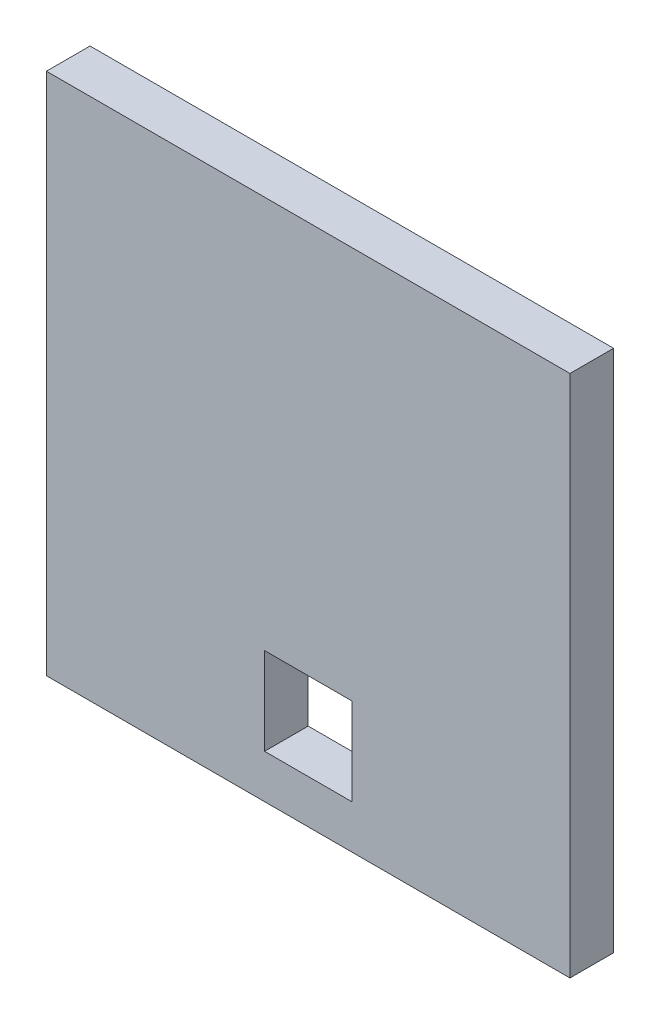
SolidWorks part; units mm, degrees
ref_plane "Front Plane" through (0, 0, 0) normal (0, 0, 1) x (1, 0, 0)
ref_plane "Top Plane" through (0, 0, 0) normal (0, 1, 0) x (1, 0, 0)
ref_plane "Right Plane" through (0, 0, 0) normal (1, 0, 0) x (0, 0, -1)
sketch "Sketch2" plane through (0, 0, 0) normal (0, 0, 1) x (1, 0, 0)
  line L1 (0, 0) -> (38.1, 0)
  line L2 (0, 0) -> (0, 38.1)
  line L3 (0, 38.1) -> (38.1, 38.1)
  line L4 (38.1, 0) -> (38.1, 38.1)
  dimension "D1" = 38.1
  dimension "D2" = 38.1
extrude "Boss-Extrude1" add sketch "Sketch2" along normal blind 3.175
sketch "Sketch8" plane through (0, 0, 3.175) normal (0, 0, 1) x (1, 0, 0)
  line L0 (0, 0) -> (38.1, 0) construction
  line L1 (15.875, 9.525) -> (22.225, 9.525)
  line L2 (15.875, 9.525) -> (15.875, 3.175)
  line L3 (15.875, 3.175) -> (22.225, 3.175)
  line L4 (22.225, 9.525) -> (22.225, 3.175)
  line L5 (38.1, 0) -> (38.1, 38.1) construction
  dimension "D1" = 6.35
  dimension "D2" = 6.35
  dimension "D3" = 3.175
  dimension "D4" = 15.875
extrude "Cut-Extrude2" cut sketch "Sketch8" against normal through all
